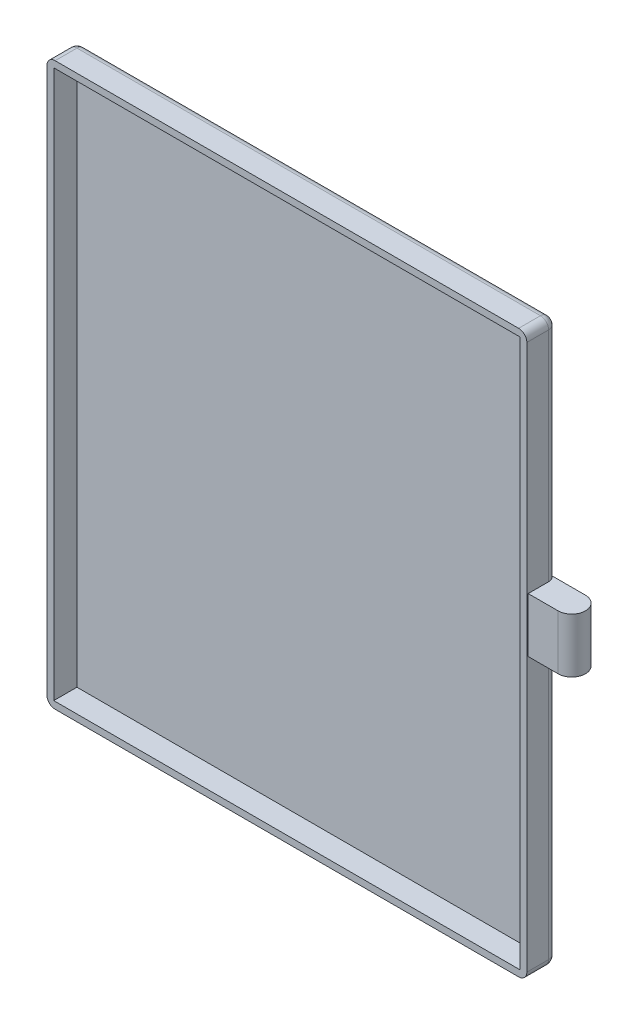
SolidWorks part; units mm, degrees
ref_plane "Front Plane" through (0, 0, 0) normal (0, 0, 1) x (1, 0, 0)
ref_plane "Top Plane" through (0, 0, 0) normal (0, 1, 0) x (1, 0, 0)
ref_plane "Right Plane" through (0, 0, 0) normal (1, 0, 0) x (0, 0, -1)
sketch "Sketch1" plane through (0, 0, 0) normal (0, 0, 1) x (1, 0, 0)
  line L1 (-44, 51.5) -> (44, 51.5)
  line L2 (-44, 51.5) -> (-44, -51.5)
  line L3 (-44, -51.5) -> (44, -51.5)
  line L4 (44, 51.5) -> (44, -51.5)
  line L5 (-44, 51.5) -> (44, -51.5) construction
  line L6 (-44, -51.5) -> (44, 51.5) construction
  point P0 (0, 0)
  dimension "D1" = 103
  dimension "D2" = 88
extrude "Boss-Extrude1" add sketch "Sketch1" along normal blind 5.5
shell "Shell1" thickness 1.25 removed face at (0, 0, 5.5)
sketch "Sketch2" plane through (44, 0, 0) normal (1, 0, 0) x (0, 0, -1)
  line L0 (-5.5, 51.5) -> (0, 51.5) construction
  line L1 (-5.25, 10) -> (-0.25, 10)
  line L2 (-5.25, 10) -> (-5.25, 0)
  line L3 (-5.25, 0) -> (-0.25, 0)
  line L4 (-0.25, 10) -> (-0.25, 0)
  line L5 (-5.25, 10) -> (-0.25, 0) construction
  line L6 (-5.25, 0) -> (-0.25, 10) construction
  point P0 (-2.75, 5)
  point P7 (-2.75, 0)
  point P8 (-2.75, 51.5)
  point P9 (0, 0)
  dimension "D1" = 10
  dimension "D2" = 5
extrude "Boss-Extrude2" add sketch "Sketch2" along normal blind 8
fillet "Fillet1" 2 edges at (52, 5, 5.25) (52, 5, 0.25) type full round first side face at (48, 5, 5.25) second side face at (48, 5, 0.25) middle face at (52, 5, 2.75)
sketch "Sketch3" plane through (0, 0, 0) normal (0, -1, 0) x (1, 0, 0)
  circle A0 centre (49.5, 2.75) radius 1.5
  dimension "D1" = 3
extrude "Cut-Extrude1" cut sketch "Sketch3" against normal blind 3
fillet "Fillet2" radius 1.5 8 edges at (-44, 0, 0) (0, -51.5, 0) (44, 0, 0) (0, 51.5, 0) (44, 51.5, 2.75) (44, -51.5, 2.75) (-44, -51.5, 2.75) (-44, 51.5, 2.75)
